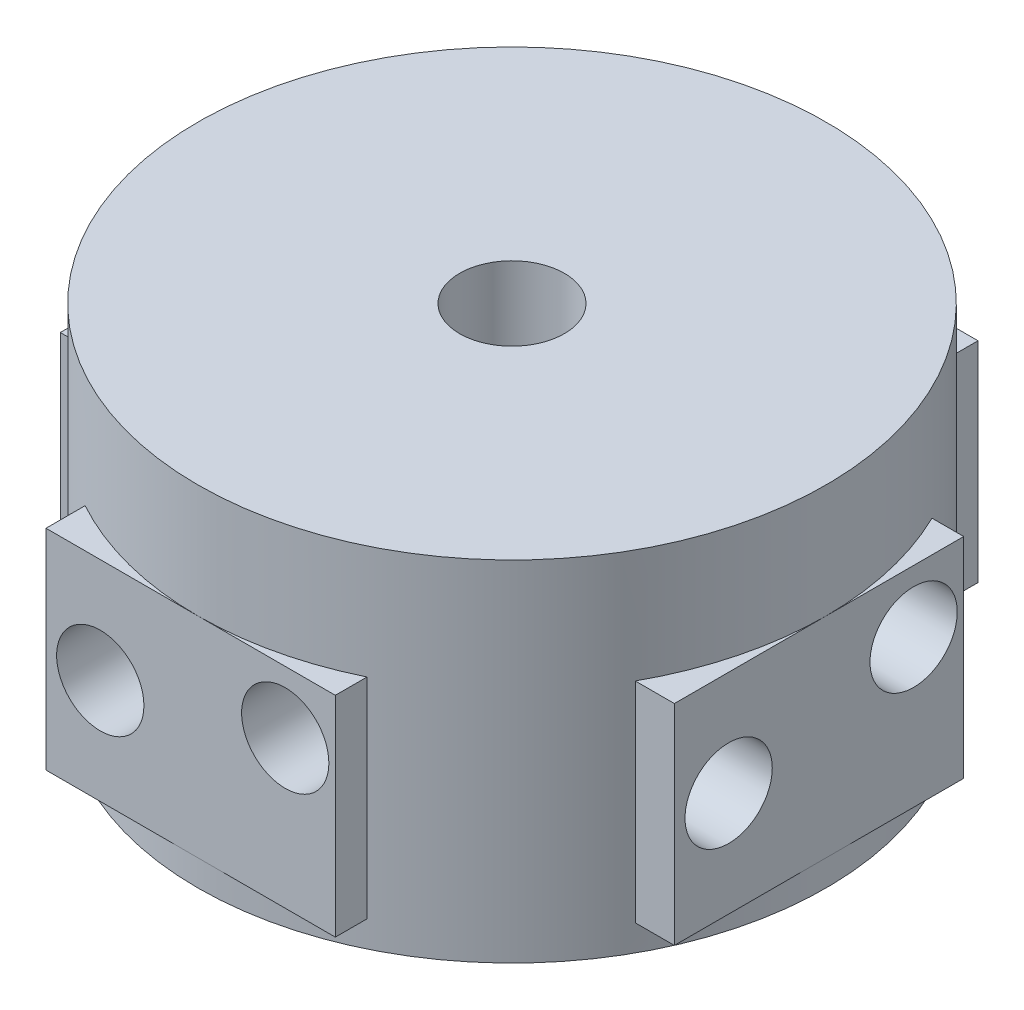
SolidWorks part; units mm, degrees
note: '?' marks a value the reader was unsure of.
ref_plane "Plan de face" through (0, 0, 0) normal (0, 0, 1) x (1, 0, 0)
ref_plane "Plan de dessus" through (0, 0, 0) normal (0, 1, 0) x (1, 0, 0)
ref_plane "Plan de droite" through (0, 0, 0) normal (1, 0, 0) x (0, 0, -1)
sketch "Esquisse1" plane through (0, 0, 0) normal (0, 1, 0) x (1, 0, 0)
  circle A0 centre (0, 0) radius 3
  circle A1 centre (0, 0) radius 18
  dimension "D2" = 6
  dimension "D1" = 15
extrude "Boss.-Extru.1" add sketch "Esquisse1" along normal blind 20
ref_axis "Axe1" through (0, 39.9113, 0) along (0, -1, 0)?
ref_plane "Plan1" through (-18, 0, 0) normal (-1, 0, 0) x (0, 0, 1)
sketch "Esquisse2" plane through (-18, 0, 0) normal (-1, 0, 0) x (0, 0, 1)
  line L0 (-5.5884, 7.5) -> (5.0085, 9.9465)
  line L1 (7.878, 13.5) -> (-8.6974, 13.5)
  line L2 (7.878, 13.5) -> (7.878, 1.5)
  line L3 (7.878, 1.5) -> (-8.6974, 1.5)
  line L4 (-8.6974, 13.5) -> (-8.6974, 1.5)
  line L5 (-5.5884, 7.5) -> (2.2192, 7.5)
  line L6 (-18, 0) -> (18, 0) construction
  circle A0 centre (-5.5884, 7.5) radius 2.5
  circle A1 centre (5.0085, 9.9465) radius 2.5
  point P8 (0, 0)
  point P12 (0, 0)
  point P13 (0, 0)
  point P15 (-4.3864, -3.1504)
  dimension "D1" = 5
  dimension "D2" = 5
  dimension "D3" = 13
  dimension "D4" = 7.5
  dimension "D5" = 6
  dimension "D6" = 12
extrude "Boss.-Extru.2" add sketch "Esquisse2" against normal up to next
sketch "Esquisse3" plane through (-18, 0, 0) normal (-1, 0, 0) x (0, 0, 1)
  circle A0 centre (5.0085, 9.9465) radius 2.5 construction
  circle A1 centre (5.0085, 9.9465) radius 2.5
  circle A2 centre (-5.5884, 7.5) radius 2.5 construction
  circle A3 centre (-5.5884, 7.5) radius 2.5
extrude "Enlèv. mat.-Extru.1" cut sketch "Esquisse3" against normal blind 8
pattern_circular "Répétition circulaire1" count 4 every 90 about axis through (0, 0, 0) along (0, 1, 0) of "Boss.-Extru.2", "Enlèv. mat.-Extru.1"
